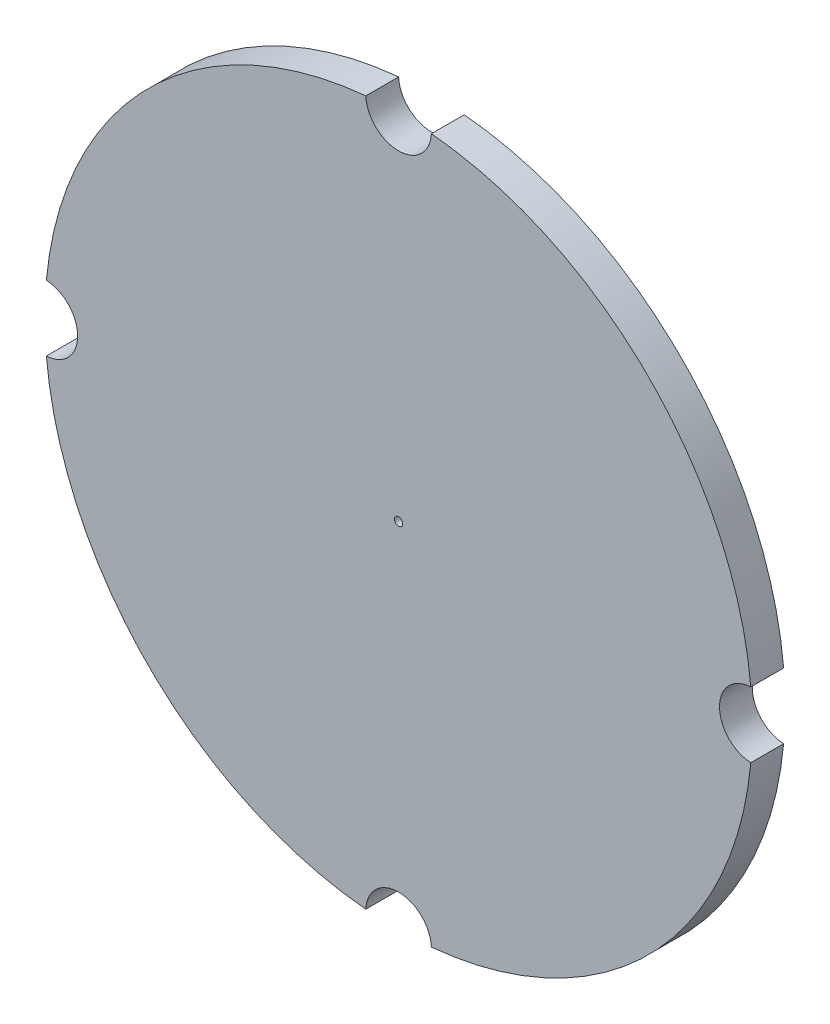
SolidWorks part; units mm, degrees
ref_plane "Front Plane" through (0, 0, 0) normal (0, 0, 1) x (1, 0, 0)
ref_plane "Top Plane" through (0, 0, 0) normal (0, 1, 0) x (1, 0, 0)
ref_plane "Right Plane" through (0, 0, 0) normal (1, 0, 0) x (0, 0, -1)
sketch "Sketch1" plane through (0, 0, 0) normal (0, 0, 1) x (1, 0, 0)
  circle A0 centre (0, 0) radius 215.5261
  circle A1 centre (215.5261, 0) radius 20
  circle A2 centre (0, -215.5261) radius 20
  circle A3 centre (0, -215.5261) radius 20
  circle A4 centre (-215.5261, 0) radius 20
  circle A5 centre (0, 215.5261) radius 20
  circle A6 centre (0, 0) radius 2.5
  point P16 (0, 0)
  dimension "D1" = 40
  dimension "D4" = 5
  dimension "D2" = 304.8
  dimension "D3" = 4
extrude "Boss-Extrude1" add sketch "Sketch1" along normal blind 20 contours A5 A0 A4 A2 A1 region at (189.4564, 0, 0)
sketch "Sketch2" plane through (0, 0, 20) normal (0, 0, 1) x (1, 0, 0)
  line L0 (0, 195.5261) -> (0, 0) construction
  circle A0 centre (0, 0) radius 195.5261 construction
  arc A8 (-19.9785, 214.5982) -> (19.9785, 214.5982) centre (0, 215.5261) ccw
  arc A9 (-19.9785, 214.5982) -> (-214.5982, 19.9785) centre (0, 0) ccw
  arc A10 (-214.5982, -19.9785) -> (-214.5982, 19.9785) centre (-215.5261, 0) ccw
  arc A11 (-214.5982, -19.9785) -> (-19.9785, -214.5982) centre (0, 0) ccw
  arc A12 (19.9785, -214.5982) -> (-19.9785, -214.5982) centre (0, -215.5261) ccw
  arc A13 (19.9785, -214.5982) -> (214.5982, -19.9785) centre (0, 0) ccw
  arc A14 (214.5982, 19.9785) -> (214.5982, -19.9785) centre (215.5261, 0) ccw
  arc A15 (214.5982, 19.9785) -> (19.9785, 214.5982) centre (0, 0) ccw
  arc A16 (-19.9785, 214.5982) -> (19.9785, 214.5982) centre (0, 215.5261) ccw
  arc A17 (-19.9785, 214.5982) -> (-214.5982, 19.9785) centre (0, 0) ccw
  arc A18 (-214.5982, -19.9785) -> (-214.5982, 19.9785) centre (-215.5261, 0) ccw
  arc A19 (-214.5982, -19.9785) -> (-19.9785, -214.5982) centre (0, 0) ccw
  arc A20 (19.9785, -214.5982) -> (-19.9785, -214.5982) centre (0, -215.5261) ccw
  arc A21 (19.9785, -214.5982) -> (214.5982, -19.9785) centre (0, 0) ccw
  arc A22 (214.5982, 19.9785) -> (214.5982, -19.9785) centre (215.5261, 0) ccw
  arc A23 (214.5982, 19.9785) -> (19.9785, 214.5982) centre (0, 0) ccw
  dimension "D1" = 0
